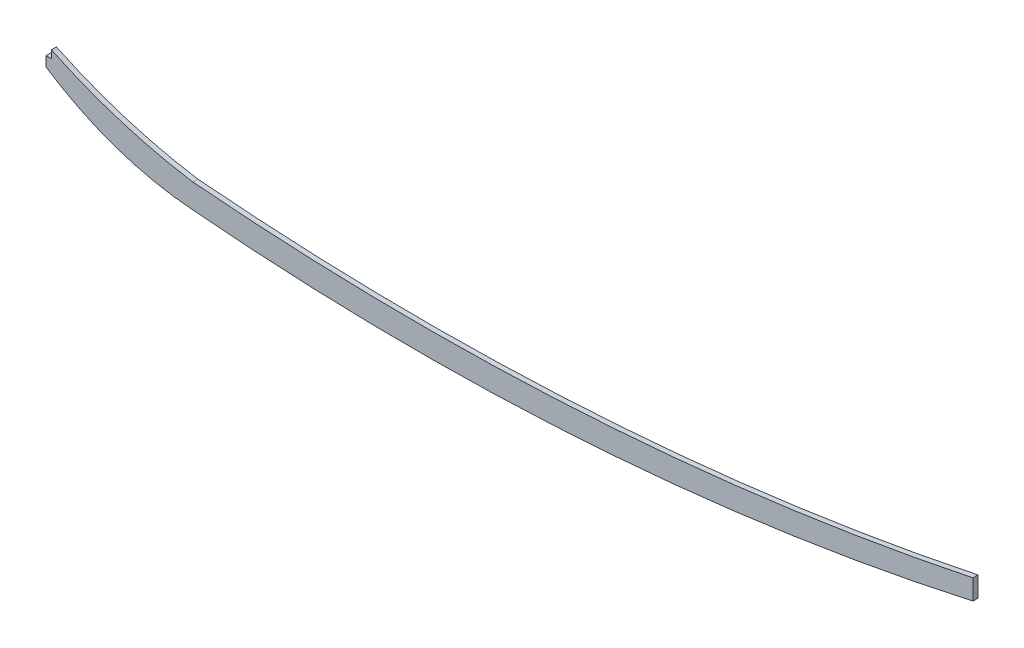
SolidWorks part; units mm, degrees
material "Balsa"
ref_plane "Front Plane" through (0, 0, 0) normal (0, 0, 1) x (1, 0, 0)
ref_plane "Top Plane" through (0, 0, 0) normal (0, 1, 0) x (1, 0, 0)
ref_plane "Right Plane" through (0, 0, 0) normal (1, 0, 0) x (0, 0, -1)
sketch "Sketch1" plane through (0, 0, 0) normal (0, 0, 1) x (1, 0, 0)
  line L3 (0, -97.563) -> (0, -84.863)
  line L4 (583.5225, -97.0036) -> (583.5225, -84.3036)
  arc A6 (0, -97.563) -> (92.3925, -129.289) centre (106.9176, 63.4069) ccw
  arc A10 (92.3925, -129.289) -> (583.5225, -97.0036) centre (233.5795, 1474.6667) ccw
  arc A17 (0, -84.863) -> (92.3925, -114.049) centre (142.0237, 203.9001) ccw
  arc A19 (92.3925, -114.049) -> (583.5225, -84.3036) centre (236.5524, 1575.136) ccw
  dimension "D1" = 193.2426
  dimension "D5" = 1610.1576
  dimension "D6" = 583.5225
  dimension "D4" = 31.726
  dimension "D10" = 15.24
  dimension "D11" = 321.7994
  dimension "D12" = 1695.3253
  dimension "D2" = 97.563
  dimension "D3" = 92.3925
  dimension "D7" = 97.0036
  dimension "D8" = 12.7
  dimension "D9" = 12.7
extrude "Boss-Extrude1" add sketch "Sketch1" along normal mid plane 3.175 contours A19 A17 L3 A6 A10 L4 region at (5.8576, -91.213, 0)
sketch "Sketch2" plane through (0, 0, 1.5875) normal (0, 0, 1) x (1, 0, 0)
  line L0 (0, 0) -> (0, -84.863) construction
  line L2 (0, -84.863) -> (3.3782, -84.863)
  line L3 (0, -84.863) -> (0, -91.34)
  line L4 (0, -91.34) -> (3.3782, -91.34)
  line L5 (3.3782, -84.863) -> (3.3782, -91.34)
  dimension "D1" = 84.863
  dimension "D2" = 6.477
  dimension "D3" = 3.3782
extrude "Cut-Extrude1" cut sketch "Sketch2" against normal through all
equation "\"slotwidth\"=0.197118"
